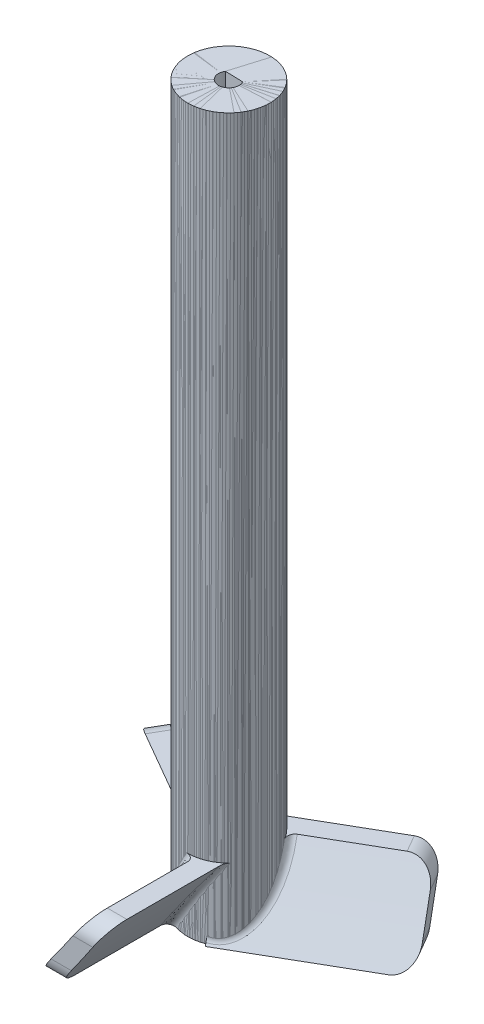
SolidWorks part; units mm, degrees
ref_plane "Front Plane" through (0, 0, 0) normal (0, 0, 1) x (1, 0, 0)
ref_plane "Top Plane" through (0, 0, 0) normal (0, 1, 0) x (1, 0, 0)
ref_plane "Right Plane" through (0, 0, 0) normal (1, 0, 0) x (0, 0, -1)
sketch "Sketch7" plane through (0, 0, 0) normal (0, 0, 1) x (1, 0, 0)
  line L0 (14.5391, 0) -> (-14.5391, 0) construction
  line L1 (6.849, 7) -> (4.9497, 7)
  line L2 (0, 0) -> (2, 0)
  arc A0 (0, 0) -> (4.9497, 7) centre (-91.3778, 69.8639) ccw
  arc A1 (6.849, 7) -> (2, 0) centre (-91.3778, 69.8639) cw
  dimension "D2" = 7
extrude "Boss-Extrude2" add sketch "Sketch7" along normal blind 15 contours A0 L1 A1 L2
fillet "Fillet1" radius 2 2 edges at (1, 0, 15) (5.8994, 7, 15)
sketch "Sketch10" plane through (0, 0, 0) normal (0, 1, 0) x (1, 0, 0)
  line L0 (0.3156, 0) -> (8.1957, 0) construction
  line L1 (4.9497, 0) -> (0, 0) construction
  line L2 (6.849, 0) -> (4.9497, 0) construction
  line L3 (2, 0) -> (6.849, 0) construction
  line L4 (4.2556, 0) -> (4.2556, -0.5251)
  line L5 (3.1481, -1000) -> (3.1481, 49000) construction
  circle A0 centre (4.2556, -0.5251) radius 3.9749
  point P5 (3.1481, 0)
  point P10 (-1.8519, 0)
  point P17 (3.1481, 0)
  dimension "D4" = 5
extrude "Boss-Extrude3" add sketch "Sketch10" along normal blind 70 contours A0 region at (0.3932, 0, 0.5251)
fillet "Fillet4" radius 0.7 2 edges at (1.2681, 1.6905, 3.147) (3.7358, 2.3821, 4.4659)
pattern_circular "CirPattern1" count 3 over 360 about axis through (4.2556, 70, 0.5251) along (0, -1, 0) of bodies 103 102
sketch "Sketch11" plane through (0, 70, 0) normal (0, 1, 0) x (1, 0, 0)
  line L0 (3.4046, 0) -> (5.1359, -0.0507)
  arc A1 (3.4046, 0) -> (5.1359, -0.0507) centre (4.2556, -0.5251) ccw
  circle A2 centre (4.2556, -0.5251) radius 3.9749 construction
extrude "Cut-Extrude1" cut sketch "Sketch11" against normal blind 40 contours A1 L0
equation "\"insidebladediameter\"=0.01"
equation "\"height\"= 0.007"
equation "\"bladethickness\"=0.002"
equation "\"insidebladeradius\"= \"insidebladediameter\" / 2"
equation "\"D1@Sketch7\"=\"bladethickness\""
equation "\"D2@Sketch7\"=\"height\""
equation "\"bladewidth\"= \"height\" * cos ( \"bladeangle\" )"
equation "\"bladelength\"= 0.015"
equation "\"D1@Boss-Extrude2\"=\"bladelength\""
equation "\"bladetipradius\"= 0.002"
equation "\"D1@Fillet1\"=\"bladetipradius\""
equation "\"fusedistance\"= 0.0045"
equation "\"motorrodheight\"=0.07"
equation "\"D1@Boss-Extrude3\"=\"motorrodheight\""
equation "\"numberofblades\"= 3"
equation "\"D1@CirPattern1\"=\"numberofblades\""
equation "\"roddiameter\"= ( \"bladewidth\" + 0.003 )"
equation "\"roddepth\"= 0.005"
equation "\"bladeangle\"= 45deg"
equation "\"m\"=1"
equation "\"flatfacedist\"= 0.0005"
equation "\"motorshaftdiameter\"=0.002"
equation "\"D1@Sketch11\"=\"motorshaftdiameter\"/2"
equation "\"D3@Sketch7\"=\"bladewidth\""
equation "\"D2@Sketch10\"=\"roddiameter\"/2-\"fusedistance\""
equation "\"D1@Sketch10\"=\"roddiameter\""
equation "\"D2@Sketch11\"=\"flatfacedist\""
equation "\"bladefilletradius\"= 0.0007"
equation "\"D1@Fillet4\"=\"bladefilletradius\""
